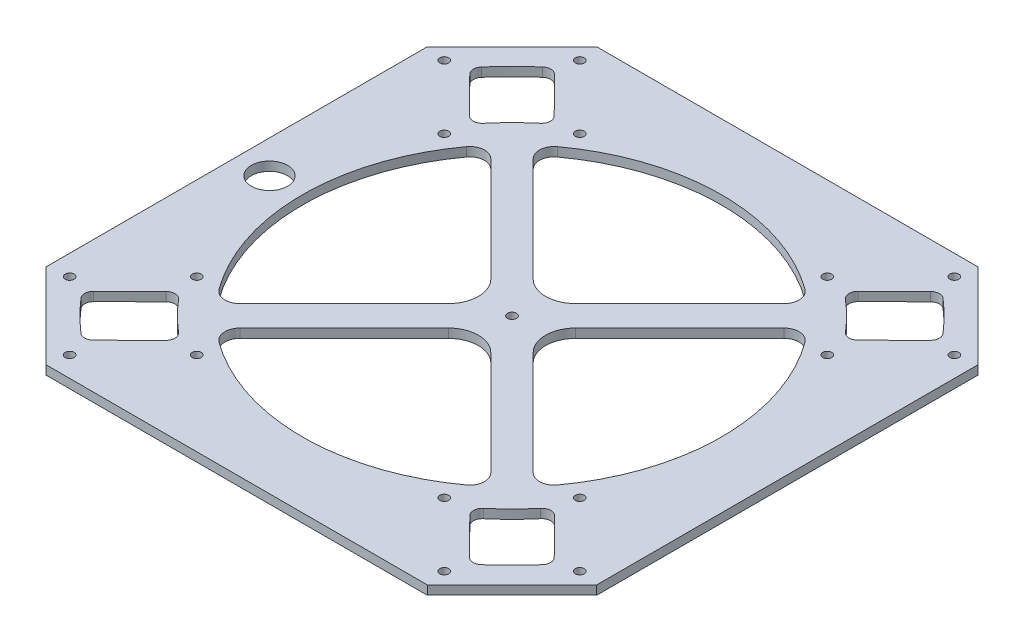
SolidWorks part; units mm, degrees
material "Thornel Mat VMA"
ref_plane "前视基准面" through (0, 0, 0) normal (0, 0, 1) x (1, 0, 0)
ref_plane "上视基准面" through (0, 0, 0) normal (0, 1, 0) x (1, 0, 0)
ref_plane "右视基准面" through (0, 0, 0) normal (1, 0, 0) x (0, 0, -1)
sketch "草图1" plane through (0, 0, 0) normal (0, 1, 0) x (1, 0, 0)
  line L0 (-63.6396, 91.9239) -> (-91.9239, 63.6396)
  line L1 (63.6396, 91.9239) -> (-63.6396, 91.9239)
  line L2 (91.9239, 63.6396) -> (91.9239, -63.6396)
  line L3 (63.6396, -91.9239) -> (-63.6396, -91.9239)
  line L4 (-91.9239, 63.6396) -> (-91.9239, -63.6396)
  line L5 (91.9239, 91.9239) -> (-91.9239, -91.9239) construction
  line L6 (91.9239, -91.9239) -> (-91.9239, 91.9239) construction
  line L7 (91.9239, -63.6396) -> (63.6396, -91.9239)
  line L8 (-91.9239, -63.6396) -> (-63.6396, -91.9239)
  line L9 (63.6396, 91.9239) -> (91.9239, 63.6396)
  line L10 (-91.9239, 91.9239) -> (-91.9239, -91.9239) construction
  line L11 (-91.9239, -91.9239) -> (91.9239, -91.9239) construction
  line L12 (91.9239, -91.9239) -> (91.9239, 91.9239) construction
  line L13 (91.9239, 91.9239) -> (-91.9239, 91.9239) construction
  point P0 (0, 0)
  dimension "D1" = 220
  dimension "D2" = 40
extrude "凸台-拉伸1" add sketch "草图1" along normal blind 3
sketch "草图11" plane through (0, 3, 0) normal (0, 1, 0) x (1, 0, 0)
  circle A0 centre (0, 0) radius 70
  dimension "D1" = 140
extrude "切除-拉伸6" cut sketch "草图11" against normal through all both and the other way through all
hole_wizard "孔1" positions "草图13" profile "草图14" legacy end condition through all
sketch "草图13" plane through (0, 0, 0) normal (0, -1, 0) x (-1, 0, 0)
  point P0 (85.1534, -62.5223)
  point P3 (63.9402, -41.3091)
  point P6 (41.3127, -63.9365)
  point P9 (62.5259, -85.1497)
  point P12 (-62.5259, -85.1497)
  point P15 (-41.3127, -63.9365)
  point P18 (-63.9402, -41.3091)
  point P21 (-85.1534, -62.5223)
  point P24 (-85.1534, 62.5296)
  point P27 (-62.5259, 85.157)
  point P30 (-41.3127, 63.9438)
  point P33 (-63.9402, 41.3164)
  point P36 (85.1534, 62.5296)
  point P39 (63.9402, 41.3164)
  point P42 (41.3127, 63.9438)
  point P45 (62.5259, 85.157)
sketch "草图14" plane through (-85.1534, 0, 62.5223) normal (1, 0, 0) x (0, 0, -1)
  line L0 (0, 0) -> (0, 3)
  line L1 (0, 3) -> (1.5, 3)
  line L2 (1.5, 3) -> (1.5, 0)
  line L3 (1.5, 0) -> (0, 0)
  line L4 (0, 110) -> (0, -10) construction
  dimension "直径" = 3
  dimension "深度" = 3
sketch "草图15" plane through (0, 3, 0) normal (0, 1, 0) x (1, 0, 0)
  line L0 (-54.5847, 45.4949) -> (-58.1891, 38.9105)
  line L1 (42.968, -57.1116) -> (54.5847, -45.4949)
  line L2 (-42.968, 57.1116) -> (-34.497, 60.9094)
  line L3 (57.1116, 42.968) -> (60.9094, 34.497)
  line L4 (57.1116, 42.968) -> (45.4949, 54.5847)
  line L5 (45.4949, 54.5847) -> (38.9105, 58.1891)
  line L6 (42.968, -57.1116) -> (34.497, -60.9094)
  line L7 (42.968, -57.1116) -> (54.5847, -45.4949)
  line L8 (-57.1116, -42.968) -> (-45.4949, -54.5847)
  line L9 (54.5847, -45.4949) -> (58.1891, -38.9105)
  line L10 (-57.1116, -42.968) -> (-60.9094, -34.497)
  line L11 (-57.1116, -42.968) -> (-45.4949, -54.5847)
  line L12 (-45.4949, -54.5847) -> (-38.9105, -58.1891)
  line L14 (-42.968, 57.1116) -> (-54.5847, 45.4949)
  line L20 (57.1116, 42.968) -> (45.4949, 54.5847)
  line L27 (-14.1421, 7.0711) -> (-48.9503, 41.8792)
  line L30 (-14.1421, -7.0711) -> (-48.9503, -41.8792)
  line L31 (7.0711, 14.1421) -> (41.8792, 48.9503)
  line L33 (-7.0711, 14.1421) -> (-41.8792, 48.9503)
  line L36 (14.1421, -7.0711) -> (48.9503, -41.8792)
  line L42 (7.0711, -14.1421) -> (41.8792, -48.9503)
  line L48 (-7.0711, -14.1421) -> (-41.8792, -48.9503)
  line L49 (14.1421, 7.0711) -> (48.9503, 41.8792)
  arc A0 (-56.5232, 41.2932) -> (-58.1891, 38.9105) centre (0, 0) ccw
  arc A1 (-34.497, 60.9094) -> (-41.2932, 56.5232) centre (0, 0) ccw
  arc A2 (-41.2932, -56.5232) -> (-38.9105, -58.1891) centre (0, 0) ccw
  arc A3 (60.9094, 34.497) -> (56.5232, 41.2932) centre (0, 0) ccw
  arc A4 (41.2932, 56.5232) -> (38.9105, 58.1891) centre (0, 0) ccw
  arc A5 (34.497, -60.9094) -> (41.2932, -56.5232) centre (0, 0) ccw
  arc A6 (56.5232, -41.2932) -> (58.1891, -38.9105) centre (0, 0) ccw
  arc A7 (-60.9094, -34.497) -> (-56.5232, -41.2932) centre (0, 0) ccw
  arc A8 (-45.8355, -52.9066) -> (-38.9105, -58.1891) centre (0, 0) ccw
  arc A9 (60.9094, 34.497) -> (52.9066, 45.8355) centre (0, 0) ccw
  arc A10 (34.497, -60.9094) -> (45.8355, -52.9066) centre (0, 0) ccw
  arc A11 (52.9066, -45.8355) -> (58.1891, -38.9105) centre (0, 0) ccw
  arc A12 (7.0711, -14.1421) -> (-7.0711, -14.1421) centre (0, -21.2132) ccw
  arc A13 (14.1421, -7.0711) -> (14.1421, 7.0711) centre (21.2132, 0) cw
  arc A14 (7.0711, 14.1421) -> (-7.0711, 14.1421) centre (0, 21.2132) cw
  arc A15 (-14.1421, -7.0711) -> (-14.1421, 7.0711) centre (-21.2132, 0) ccw
  circle A16 centre (0, 0) radius 70 construction
  arc A17 (56.5232, -41.2932) -> (48.9503, -41.8792) centre (52.4858, -38.3437) cw
  arc A18 (41.8792, -48.9503) -> (41.2932, -56.5232) centre (38.3437, -52.4858) cw
  arc A19 (56.5232, 41.2932) -> (48.9503, 41.8792) centre (52.4858, 38.3437) ccw
  arc A20 (41.2932, 56.5232) -> (41.8792, 48.9503) centre (38.3437, 52.4858) cw
  arc A21 (-41.2932, 56.5232) -> (-41.8792, 48.9503) centre (-38.3437, 52.4858) ccw
  arc A22 (-48.9503, 41.8792) -> (-56.5232, 41.2932) centre (-52.4858, 38.3437) ccw
  arc A23 (-41.8792, -48.9503) -> (-41.2932, -56.5232) centre (-38.3437, -52.4858) ccw
  arc A24 (-48.9503, -41.8792) -> (-56.5232, -41.2932) centre (-52.4858, -38.3437) cw
  point P1 (0, 0)
  point P11 (0, 0)
  point P16 (0, 0)
  point P21 (0, 0)
  point P58 (0, 0)
  circle M25 centre (0, 0) radius 70
  dimension "D1" = 10
  dimension "D4" = 5
  dimension "D2" = 4
  dimension "D3" = 4
extrude "凸台-拉伸5" add sketch "草图15" against normal up to surface (3 mm away) contours A15 L30 L48 A12 L42 L36 A13 L49 L31 A14 L33 L27 M25 | L8 L12 L10 M25 | L1 L9 L6 M25 | L4 L5 L3 M25 | L2 L14 L0 M25 region at (-47.2019, 3, -51.7628) region at (0, 3, 0) region at (-51.7628, 3, 47.2019) region at (51.7628, 3, -47.2019) region at (47.2019, 3, 51.7628) up to face at (-85.1534, 0, 61.0223)
hole_wizard "孔2" positions "草图16" profile "草图17" legacy end condition through all
sketch "草图16" plane through (0, 0, 0) normal (0, -1, 0) x (-1, 0, 0)
  point P0 (0, 0)
sketch "草图17" plane through (0, 0, 0) normal (1, 0, 0) x (0, 0, -1)
  line L0 (0, 0) -> (0, 3)
  line L1 (0, 3) -> (1.5, 3)
  line L2 (1.5, 3) -> (1.5, 0)
  line L3 (1.5, 0) -> (0, 0)
  line L4 (0, 110) -> (0, -10) construction
  dimension "直径" = 3
  dimension "深度" = 3
sketch "草图20" plane through (0, 3, 0) normal (0, 1, 0) x (1, 0, 0)
  line L0 (55.8614, 55.8614) -> (77.7817, 77.7817) construction
  line L1 (64.8107, 50.7195) -> (76.9107, 62.7268)
  line L3 (50.7195, -64.8107) -> (62.7268, -76.9107)
  line L4 (50.6805, 64.8737) -> (62.7878, 76.8882)
  line L5 (62.453, 48.3799) -> (64.7375, 78.823) construction
  line L6 (78.8741, 64.6752) -> (48.3019, 62.5134) construction
  line L7 (64.8737, -50.6805) -> (76.8882, -62.7878)
  line L8 (55.8614, -55.8614) -> (77.7817, -77.7817) construction
  line L9 (48.3799, -62.453) -> (78.823, -64.7375) construction
  line L10 (64.6752, -78.8741) -> (62.5134, -48.3019) construction
  line L11 (-64.8107, -50.7195) -> (-76.9107, -62.7268)
  line L12 (-50.6805, -64.8737) -> (-62.7878, -76.8882)
  line L13 (-55.8614, -55.8614) -> (-77.7817, -77.7817) construction
  line L14 (-62.453, -48.3799) -> (-64.7375, -78.823) construction
  line L15 (-78.8741, -64.6752) -> (-48.3019, -62.5134) construction
  line L16 (-50.7195, 64.8107) -> (-62.7268, 76.9107)
  line L17 (-64.8737, 50.6805) -> (-76.8882, 62.7878)
  line L18 (-55.8614, 55.8614) -> (-77.7817, 77.7817) construction
  line L19 (-48.3799, 62.453) -> (-78.823, 64.7375) construction
  line L20 (-64.6752, 78.8741) -> (-62.5134, 48.3019) construction
  line L21 (91.9239, 63.6396) -> (63.6396, 91.9239) construction
  arc A0 (77.0641, 66.8216) -> (66.8676, 77.0242) centre (0, 0) ccw
  arc A1 (60.4037, 50.9155) -> (50.8621, 60.4487) centre (0, 0) ccw
  arc A3 (64.8107, 50.7195) -> (60.4037, 50.9155) centre (62.6976, 52.849) cw
  arc A4 (76.9107, 62.7268) -> (77.0641, 66.8216) centre (74.7975, 64.8562) ccw
  arc A5 (66.8676, 77.0242) -> (62.7878, 76.8882) centre (64.9009, 74.7588) ccw
  arc A6 (50.8621, 60.4487) -> (50.6805, 64.8737) centre (52.7936, 62.7442) cw
  arc A7 (66.8216, -77.0641) -> (77.0242, -66.8676) centre (0, 0) ccw
  arc A8 (50.9155, -60.4037) -> (60.4487, -50.8621) centre (0, 0) ccw
  arc A9 (50.7195, -64.8107) -> (50.9155, -60.4037) centre (52.849, -62.6976) cw
  arc A10 (62.7268, -76.9107) -> (66.8216, -77.0641) centre (64.8562, -74.7975) ccw
  arc A11 (77.0242, -66.8676) -> (76.8882, -62.7878) centre (74.7588, -64.9009) ccw
  arc A12 (60.4487, -50.8621) -> (64.8737, -50.6805) centre (62.7442, -52.7936) cw
  arc A13 (-77.0641, -66.8216) -> (-66.8676, -77.0242) centre (0, 0) ccw
  arc A14 (-60.4037, -50.9155) -> (-50.8621, -60.4487) centre (0, 0) ccw
  arc A15 (-64.8107, -50.7195) -> (-60.4037, -50.9155) centre (-62.6976, -52.849) cw
  arc A16 (-76.9107, -62.7268) -> (-77.0641, -66.8216) centre (-74.7975, -64.8562) ccw
  arc A17 (-66.8676, -77.0242) -> (-62.7878, -76.8882) centre (-64.9009, -74.7588) ccw
  arc A18 (-50.8621, -60.4487) -> (-50.6805, -64.8737) centre (-52.7936, -62.7442) cw
  arc A19 (-66.8216, 77.0641) -> (-77.0242, 66.8676) centre (0, 0) ccw
  arc A20 (-50.9155, 60.4037) -> (-60.4487, 50.8621) centre (0, 0) ccw
  arc A21 (-50.7195, 64.8107) -> (-50.9155, 60.4037) centre (-52.849, 62.6976) cw
  arc A22 (-62.7268, 76.9107) -> (-66.8216, 77.0641) centre (-64.8562, 74.7975) ccw
  arc A23 (-77.0242, 66.8676) -> (-76.8882, 62.7878) centre (-74.7588, 64.9009) ccw
  arc A24 (-60.4487, 50.8621) -> (-64.8737, 50.6805) centre (-62.7442, 52.7936) cw
  point P4 (0, 0)
  point P5 (63.5947, 63.5947)
  point P23 (0, 0)
  point P24 (77.7817, 77.7817)
  point P26 (63.5947, -63.5947)
  point P45 (-63.5947, -63.5947)
  point P64 (-63.5947, 63.5947)
  point P82 (0, 0)
  dimension "D1" = 79
  dimension "D2" = 102
  dimension "D4" = 3
  dimension "D3" = 20
  dimension "D5" = 4
extrude "切除-拉伸7" cut sketch "草图20" against normal through all both and the other way through all
sketch "草图21" plane through (0, 3, 0) normal (0, 1, 0) x (1, 0, 0)
  line L0 (-91.9239, 0) -> (-70, 0) construction
  line L1 (-91.9239, 63.6396) -> (-91.9239, -63.6396) construction
  circle A0 centre (-80.9686, 0) radius 6.05
  arc A1 (-56.5232, 41.2932) -> (-56.5232, -41.2932) centre (0, 0) ccw construction
  point P9 (0, 0)
  dimension "D1" = 12.1
extrude "切除-拉伸8" cut sketch "草图21" against normal through all both and the other way through all
